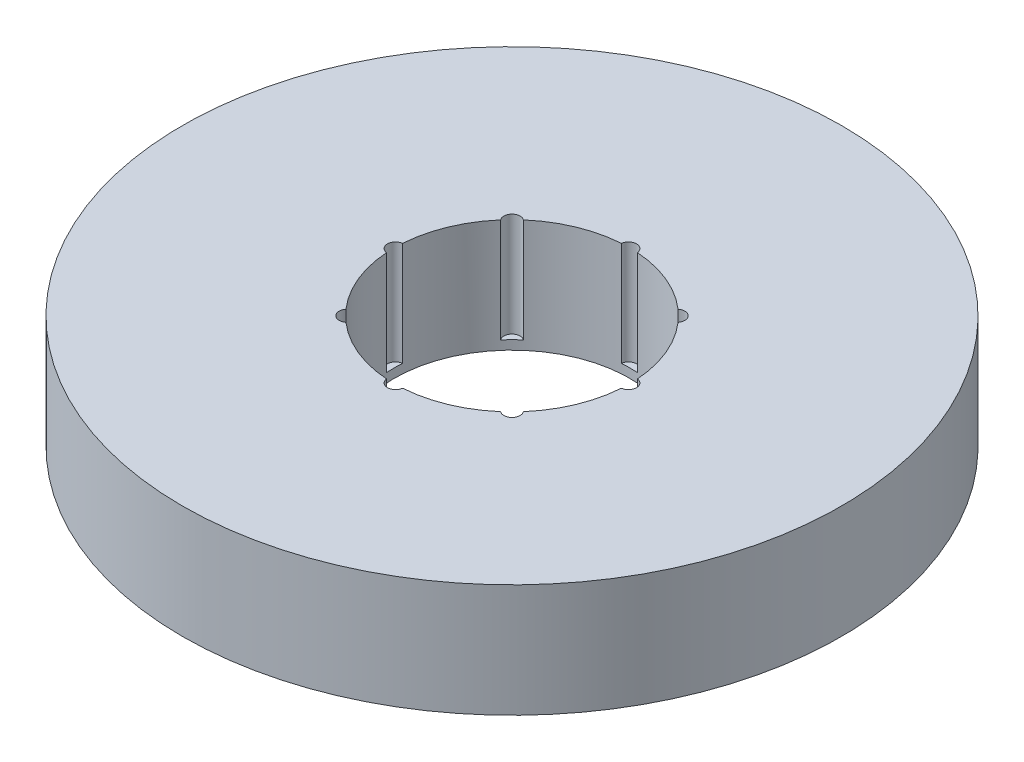
SolidWorks part; units mm, degrees
ref_plane "Front Plane" through (0, 0, 0) normal (0, 0, 1) x (1, 0, 0)
ref_plane "Top Plane" through (0, 0, 0) normal (0, 1, 0) x (1, 0, 0)
ref_plane "Right Plane" through (0, 0, 0) normal (1, 0, 0) x (0, 0, -1)
sketch "Sketch1" plane through (0, 0, 0) normal (0, 1, 0) x (1, 0, 0)
  circle A0 centre (0, 0) radius 70
  dimension "FLANGE_OD" = 140
extrude "Boss-Extrude1" add sketch "Sketch1" along normal blind 24
sketch "Sketch2" plane through (0, 0, 0) normal (0, 1, 0) x (1, 0, 0)
  circle A0 centre (0, 0) radius 25
  dimension "BORE_D" = 50
extrude "Cut-Extrude1" cut sketch "Sketch2" along normal through all
sketch "Sketch3" plane through (0, 24, 0) normal (0, 1, 0) x (1, 0, 0)
  circle A0 centre (0, 0) radius 24.7356 construction
  circle A1 centre (-24.7356, 0) radius 1.7221
  dimension "BOLT_D" = 3.4441
  dimension "BOLT_PCD" = 49.4713
extrude "Cut-Extrude2" cut sketch "Sketch3" against normal blind 22.0767
pattern_circular "CirPattern1" count 8 over 360 about axis through (0, 0, 0) along (0, 1, 0) of "Cut-Extrude2"
